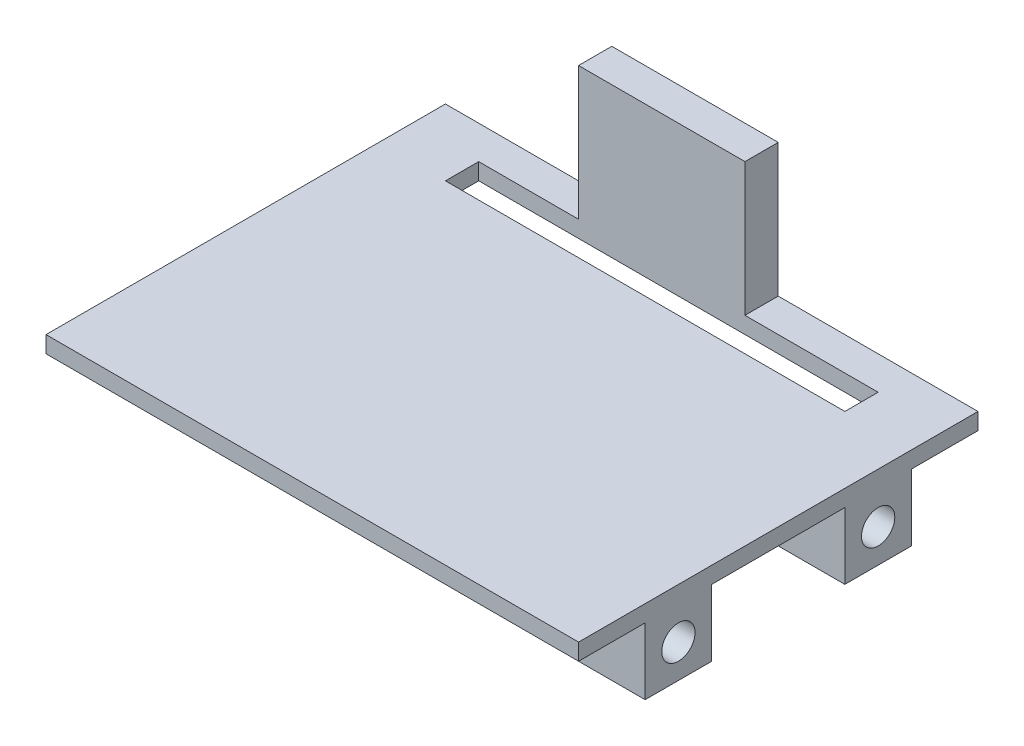
SolidWorks part; units mm, degrees
ref_plane "Front Plane" through (0, 0, 0) normal (0, 0, 1) x (1, 0, 0)
ref_plane "Top Plane" through (0, 0, 0) normal (0, 1, 0) x (1, 0, 0)
ref_plane "Right Plane" through (0, 0, 0) normal (1, 0, 0) x (0, 0, -1)
sketch "Sketch2" plane through (0, 0, 0) normal (0, 1, 0) x (1, 0, 0)
  line L1 (-101.6, -76.2) -> (101.6, -76.2)
  line L2 (-101.6, -76.2) -> (-101.6, 76.2)
  line L3 (-101.6, 76.2) -> (101.6, 76.2)
  line L4 (101.6, -76.2) -> (101.6, 76.2)
  line L5 (-101.6, -76.2) -> (101.6, 76.2) construction
  line L6 (-101.6, 76.2) -> (101.6, -76.2) construction
  point P0 (0, 0)
  dimension "D1" = 203.2
  dimension "D2" = 152.4
extrude "Boss-Extrude1" add sketch "Sketch2" along normal blind 6.35
sketch "Sketch3" plane through (0, 6.35, 0) normal (0, 1, 0) x (1, 0, 0)
  line L0 (-101.6, 0) -> (101.6, 0) construction
  line L1 (-101.6, 76.2) -> (-101.6, -76.2) construction
  line L2 (101.6, -76.2) -> (101.6, 76.2) construction
  line L3 (0, 76.2) -> (0, -76.2) construction
  line L4 (101.6, 76.2) -> (-101.6, 76.2) construction
  line L5 (-101.6, -76.2) -> (101.6, -76.2) construction
  line L7 (-76.2, 63.5) -> (76.2, 63.5)
  line L8 (-76.2, 63.5) -> (-76.2, 50.8)
  line L9 (-76.2, 50.8) -> (76.2, 50.8)
  line L10 (76.2, 63.5) -> (76.2, 50.8)
  line L11 (-76.2, 63.5) -> (76.2, 50.8) construction
  line L12 (-76.2, 50.8) -> (76.2, 63.5) construction
  point P12 (0, 57.15)
  dimension "D1" = 12.7
  dimension "D2" = 152.4
  dimension "D3" = 12.7
extrude "Cut-Extrude1" cut sketch "Sketch3" against normal blind 6.35
sketch "Sketch4" plane through (0, 0, 0) normal (0, -1, 0) x (1, 0, 0)
  line L0 (-101.6, -76.2) -> (-101.6, 76.2) construction
  line L1 (-101.6, 50.8) -> (-50.8, 50.8)
  line L2 (-101.6, 50.8) -> (-101.6, 25.4)
  line L3 (-101.6, 25.4) -> (-50.8, 25.4)
  line L4 (-50.8, 50.8) -> (-50.8, 25.4)
  line L5 (0, 76.2) -> (0, -76.2) construction
  line L6 (-101.6, 76.2) -> (101.6, 76.2) construction
  line L7 (101.6, -76.2) -> (-101.6, -76.2) construction
  line L8 (-101.6, 0) -> (101.6, 0) construction
  line L9 (101.6, 76.2) -> (101.6, -76.2) construction
  line L10 (101.6, 25.4) -> (50.8, 25.4)
  line L11 (50.8, 50.8) -> (50.8, 25.4)
  line L12 (101.6, 50.8) -> (50.8, 50.8)
  line L13 (101.6, 50.8) -> (101.6, 25.4)
  line L14 (101.6, -50.8) -> (101.6, -25.4)
  line L15 (101.6, -50.8) -> (50.8, -50.8)
  line L16 (50.8, -50.8) -> (50.8, -25.4)
  line L17 (101.6, -25.4) -> (50.8, -25.4)
  line L18 (-101.6, -25.4) -> (-50.8, -25.4)
  line L19 (-50.8, -50.8) -> (-50.8, -25.4)
  line L20 (-101.6, -50.8) -> (-50.8, -50.8)
  line L21 (-101.6, -50.8) -> (-101.6, -25.4)
  dimension "D1" = 25.4
  dimension "D2" = 50.8
  dimension "D3" = 25.4
sketch "Sketch6" plane through (0, 0, 0) normal (0, -1, 0) x (1, 0, 0)
  line L0 (0, -50.8) -> (0, -63.5) construction
  line L1 (-76.2, -50.8) -> (76.2, -50.8) construction
  line L2 (76.2, -63.5) -> (-76.2, -63.5) construction
extrude "Boss-Extrude2" add sketch "Sketch4" along normal blind 25.4
sketch "Sketch7" plane through (-101.6, 0, 0) normal (-1, 0, 0) x (0, 0, 1)
  line L0 (-38.1, -25.4) -> (-38.1, 6.35) construction
  line L1 (-25.4, -25.4) -> (-50.8, -25.4) construction
  line L2 (-76.2, 6.35) -> (76.2, 6.35) construction
  line L3 (-50.8, -12.7) -> (-25.4, -12.7) construction
  line L4 (-50.8, -25.4) -> (-50.8, 0) construction
  line L5 (-25.4, -25.4) -> (-25.4, 0) construction
  line L6 (38.1, -25.4) -> (38.1, 6.35) construction
  line L7 (50.8, -25.4) -> (25.4, -25.4) construction
  line L8 (25.4, -12.7) -> (50.8, -12.7) construction
  line L9 (25.4, -25.4) -> (25.4, 0) construction
  line L10 (50.8, -25.4) -> (50.8, 0) construction
  circle A0 centre (-38.1, -12.7) radius 6.35
  circle A1 centre (38.1, -12.7) radius 6.35
  dimension "D1" = 12.7
  dimension "D2" = 12.7
extrude "Cut-Extrude2" cut sketch "Sketch7" against normal blind 50.8
sketch "Sketch8" plane through (101.6, 0, 0) normal (1, 0, 0) x (0, 0, -1)
  line L0 (-50.8, -12.7) -> (50.8, -12.7) construction
  line L1 (-50.8, -25.4) -> (-50.8, 0) construction
  line L2 (50.8, -25.4) -> (50.8, 0) construction
  line L3 (-38.1, -25.4) -> (-38.1, 6.35) construction
  line L4 (50.8, -25.4) -> (25.4, -25.4) construction
  line L5 (38.1, -25.4) -> (38.1, 6.35) construction
  line L6 (-76.2, 6.35) -> (76.2, 6.35) construction
  line L7 (-25.4, -25.4) -> (-50.8, -25.4) construction
  circle A0 centre (-38.1, -12.7) radius 6.35
  circle A1 centre (38.1, -12.7) radius 6.35
  dimension "D1" = 12.7
  dimension "D2" = 12.7
extrude "Cut-Extrude3" cut sketch "Sketch8" against normal blind 50.8
ref_plane "Plane1" through (0, 0, 0) normal (-1, 0, 0) x (0, 0, 1)
ref_point "Point1"
sketch "Sketch12" plane through (0, 6.35, 0) normal (0, 1, 0) x (1, 0, 0)
  line L0 (101.6, 76.2) -> (-101.6, 76.2) construction
  line L1 (-38.1204, 76.2) -> (25.3796, 76.2)
  line L2 (-38.1204, 76.2) -> (-38.1204, 63.5)
  line L3 (-38.1204, 63.5) -> (25.3796, 63.5)
  line L4 (25.3796, 76.2) -> (25.3796, 63.5)
  line L5 (76.2, 63.5) -> (-76.2, 63.5) construction
  dimension "D1" = 63.5
extrude "Boss-Extrude3" add sketch "Sketch12" along normal blind 50.8
